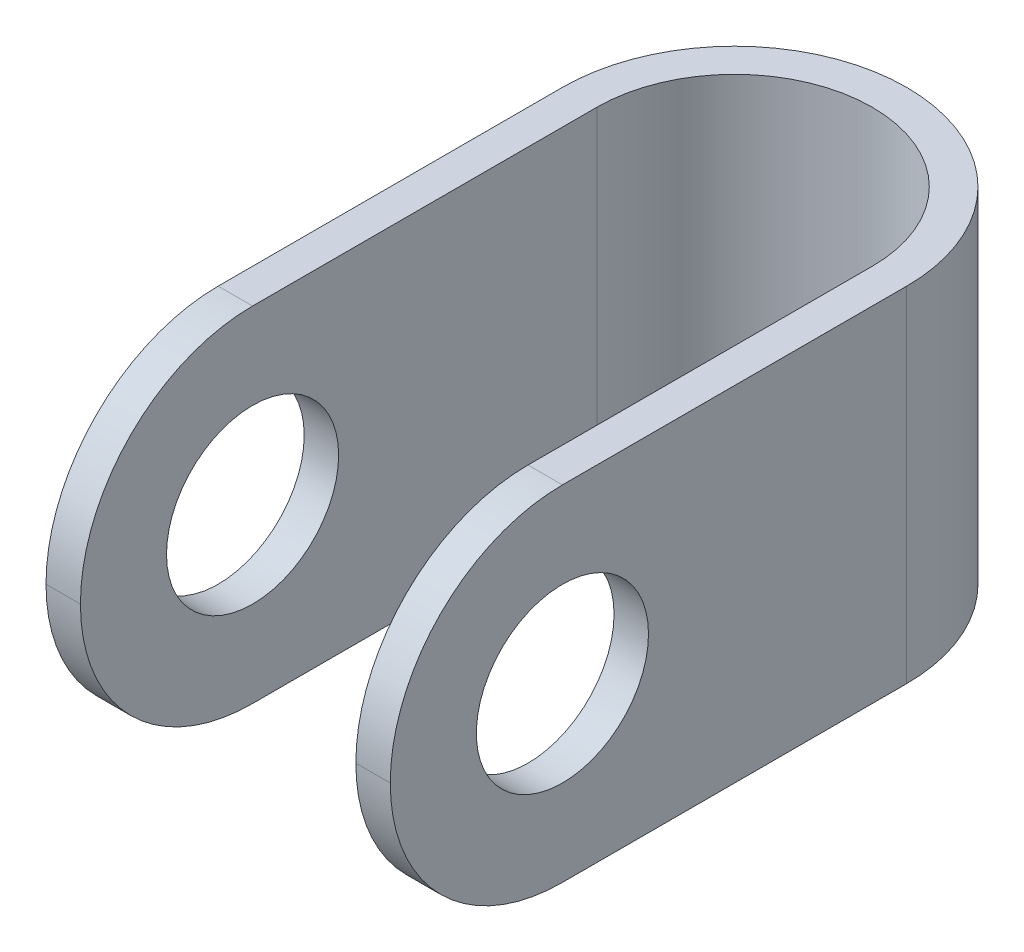
SolidWorks part; units mm, degrees
material "201 Annealed Stainless Steel (SS)"
ref_plane "Front Plane" through (0, 0, 0) normal (0, 0, 1) x (1, 0, 0)
ref_plane "Top Plane" through (0, 0, 0) normal (0, 1, 0) x (1, 0, 0)
ref_plane "Right Plane" through (0, 0, 0) normal (1, 0, 0) x (0, 0, -1)
sketch "Sketch1" plane through (0, 0, 0) normal (0, 1, 0) x (1, 0, 0)
  line L0 (0, 0) -> (0, 12)
  line L1 (0, 0) -> (-6.4, 0) construction
  line L2 (-6.4, 0) -> (-6.4, 12)
  line L3 (0.8, 0) -> (0.8, 12)
  line L4 (-7.2, 0) -> (-7.2, 12)
  line L5 (-6.4, 0) -> (-7.2, 0)
  line L6 (0, 0) -> (0.8, 0)
  arc A0 (-6.4, 12) -> (0, 12) centre (-3.2, 12) cw
  arc A1 (-7.2, 12) -> (0.8, 12) centre (-3.2, 12) cw
  dimension "D1" = 6.4
  dimension "D2" = 0.8
  dimension "D3" = 0.8
  dimension "D4" = 12
extrude "Boss-Extrude1" add sketch "Sketch1" along normal blind 8
fillet "Fillet1" radius 4 1 edges at (0.4, 8, 0)
fillet "Fillet2" radius 4 1 edges at (0.4, 0, 0)
fillet "Fillet3" radius 4 2 edges at (-6.8, 0, 0) (-6.8, 8, 0)
sketch "Sketch2" plane through (0.8, 0, 0) normal (1, 0, 0) x (0, 0, -1)
  line L0 (0, 4) -> (4, 4) construction
  circle A0 centre (4, 4) radius 2
  dimension "D2" = 4
  dimension "D1" = 4
extrude "Cut-Extrude1" cut sketch "Sketch2" against normal through all
